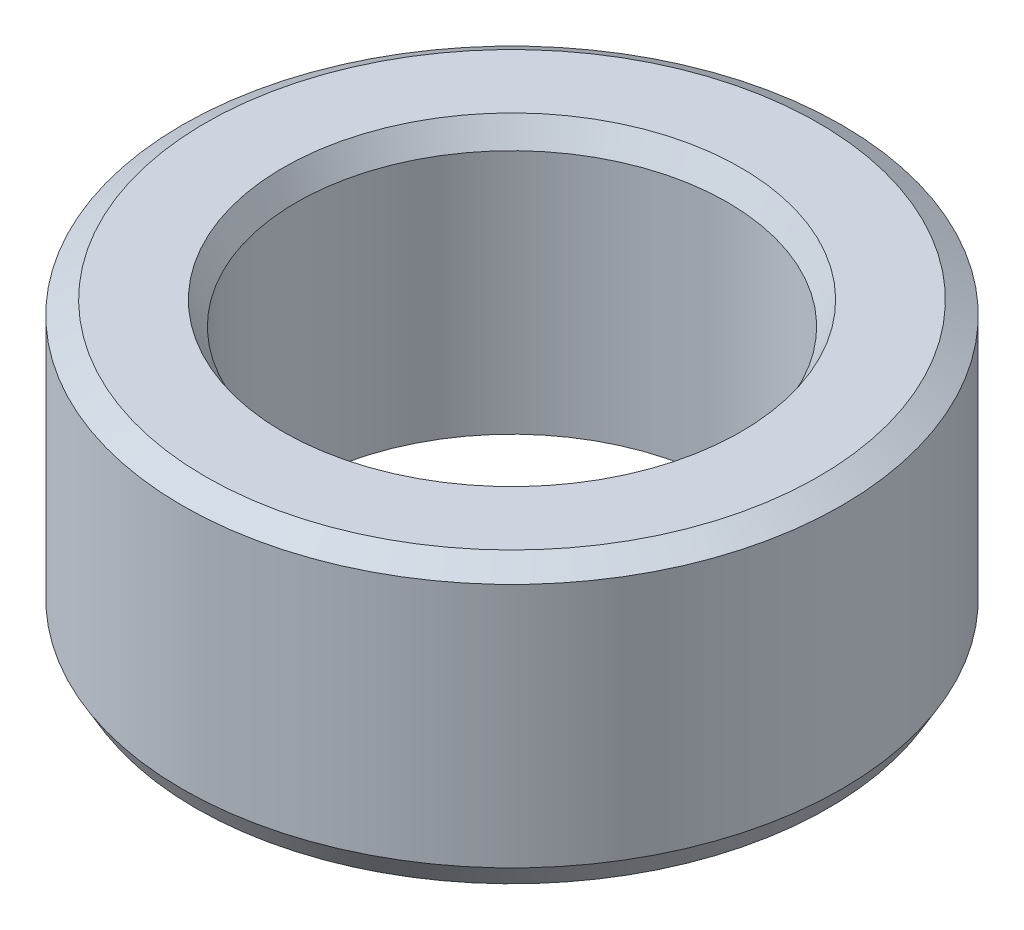
SolidWorks part; units mm, degrees
ref_plane "Front Plane" through (0, 0, 0) normal (0, 0, 1) x (1, 0, 0)
ref_plane "Top Plane" through (0, 0, 0) normal (0, 1, 0) x (1, 0, 0)
ref_plane "Right Plane" through (0, 0, 0) normal (1, 0, 0) x (0, 0, -1)
sketch "Sketch1" plane through (0, 0, 0) normal (0, 1, 0) x (1, 0, 0)
  circle A0 centre (0, 0) radius 50
  dimension "SLEEVE_OD" = 100
extrude "Boss-Extrude1" add sketch "Sketch1" along normal blind 42.7885
sketch "Sketch2" plane through (0, 0, 0) normal (0, 1, 0) x (1, 0, 0)
  circle A0 centre (0, 0) radius 32.6728
  dimension "BORE_D" = 65.3457
extrude "Cut-Extrude1" cut sketch "Sketch2" along normal through all
chamfer "Chamfer1" distance 2.0338 angle 60 4 edges at (0, 42.7885, 32.6728) (0, 0, 32.6728) (0, 0, 50) (0, 42.7885, 50) first distance on face at (0, 42.7885, 32.6728) first distance on face at (0, 0, 32.6728) first distance on face at (0, 42.7885, 50)
